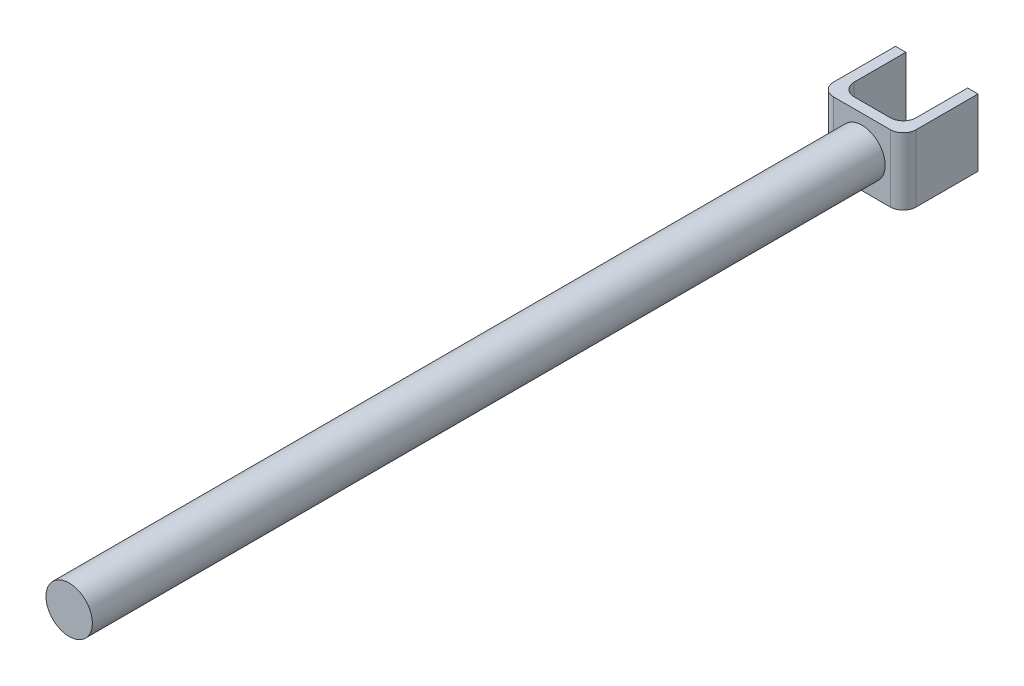
SolidWorks part; units mm, degrees
ref_plane "Front Plane" through (0, 0, 0) normal (0, 0, 1) x (1, 0, 0)
ref_plane "Top Plane" through (0, 0, 0) normal (0, 1, 0) x (1, 0, 0)
ref_plane "Right Plane" through (0, 0, 0) normal (1, 0, 0) x (0, 0, -1)
sketch "Sketch1" plane through (0, 0, 0) normal (0, 1, 0) x (1, 0, 0)
  line L0 (0, 0) -> (0, -20.7763) construction
  line L1 (7, -20.7763) -> (-7, -20.7763)
  line L2 (12, -15.7763) -> (12, 4.2237)
  line L3 (12, 4.2237) -> (16, 4.2237)
  line L4 (16, 4.2237) -> (16, -19.7763)
  line L5 (11, -24.7763) -> (-11, -24.7763)
  line L6 (-16, 4.2237) -> (-16, -19.7763)
  line L7 (-12, 4.2237) -> (-16, 4.2237)
  line L8 (-12, -15.7763) -> (-12, 4.2237)
  arc A0 (16, -19.7763) -> (11, -24.7763) centre (11, -19.7763) cw
  arc A1 (7, -20.7763) -> (12, -15.7763) centre (7, -15.7763) ccw
  arc A2 (-7, -20.7763) -> (-12, -15.7763) centre (-7, -15.7763) cw
  arc A3 (-16, -19.7763) -> (-11, -24.7763) centre (-11, -19.7763) ccw
  point P6 (0, -20.7763)
  point P13 (12, -20.7763)
  point P20 (0, -24.7763)
  point P22 (-12, -20.7763)
  dimension "D5" = 5
  dimension "D1" = 4
  dimension "D2" = 4
  dimension "D3" = 25
  dimension "D4" = 12
extrude "Boss-Extrude1" add sketch "Sketch1" along normal blind 13 and the other way blind 13
sketch "Sketch2" plane through (0, 0, 24.7763) normal (0, 0, 1) x (1, 0, 0)
  circle A0 centre (0, 0) radius 9
  dimension "D1" = 18
extrude "Boss-Extrude2" add sketch "Sketch2" along normal blind 307.5
sketch "Sketch3" plane through (0, 0, 0) normal (0, 1, 0) x (1, 0, 0)
  line L0 (0, 0) -> (0, -400) construction
  point P4 (0, -400)
  point P5 (0, 0)
  dimension "D1" = 400
